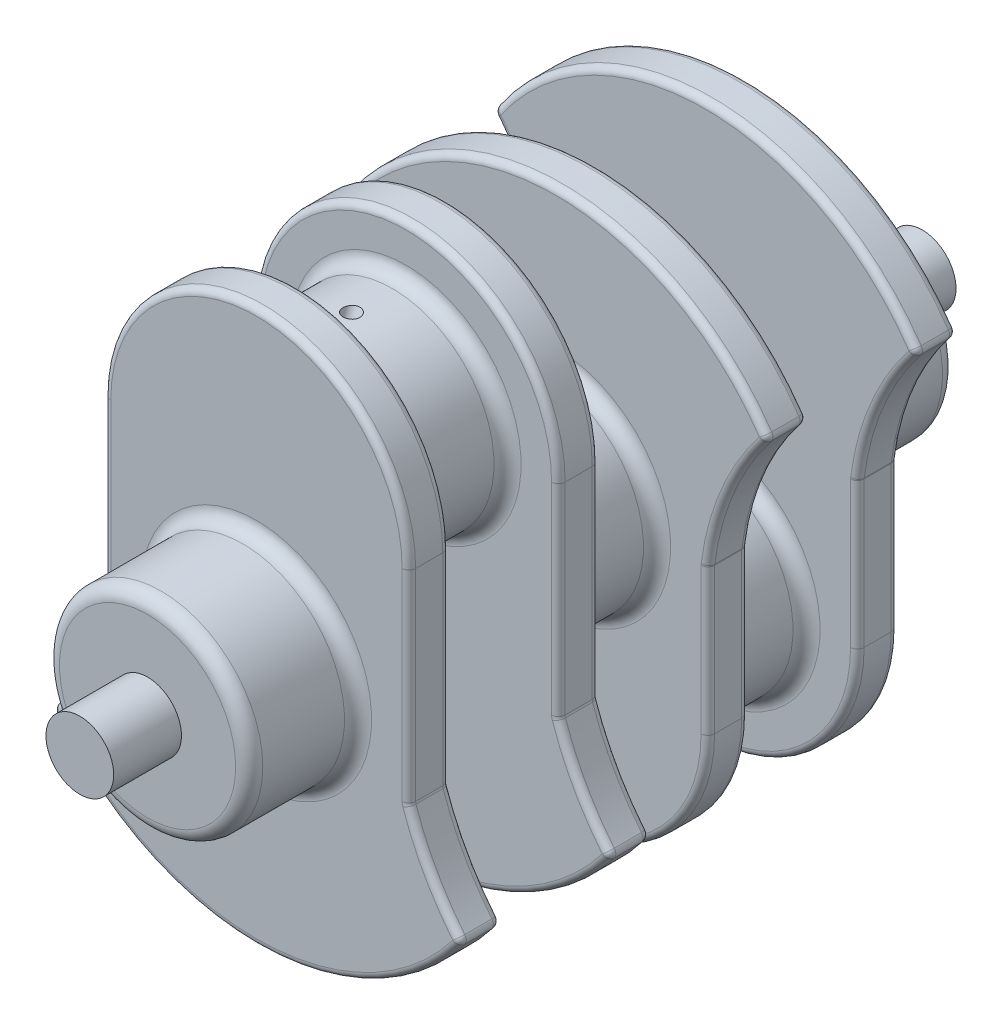
SolidWorks part; units mm, degrees
material "AISI 4340 Steel, normalized"
ref_plane "Front Plane" through (0, 0, 0) normal (0, 0, 1) x (1, 0, 0)
ref_plane "Top Plane" through (0, 0, 0) normal (0, 1, 0) x (1, 0, 0)
ref_plane "Right Plane" through (0, 0, 0) normal (1, 0, 0) x (0, 0, -1)
sketch "Sketch1" plane through (0, 0, 0) normal (0, 0, 1) x (1, 0, 0)
  circle A0 centre (0, 0) radius 30
  dimension "D1" = 30
extrude "Boss-Extrude1" add sketch "Sketch1" along normal blind 32.13
sketch "Sketch8" plane through (0, 0, 0) normal (0, 0, -1) x (-1, 0, 0)
  line L0 (-45, 43.2) -> (-45, -16.687)
  line L1 (45, 43.2) -> (45, -16.687)
  arc A0 (45, 43.2) -> (-45, 43.2) centre (0, 43.2) ccw
  arc A5 (-60.4975, -44.3289) -> (60.4975, -44.3289) centre (0, 0) ccw
  arc A6 (-45, -16.687) -> (-60.4975, -44.3289) centre (-125, 10) cw
  arc A7 (45, -16.687) -> (60.4975, -44.3289) centre (125, 10) ccw
  dimension "D1" = 45
  dimension "D2" = 75
  dimension "D3" = 43.2
  dimension "D5" = 10
  dimension "D6" = 125
extrude "Boss-Extrude5" add sketch "Sketch8" along normal blind 12
sketch "Sketch2" plane through (0, 0, 32.13) normal (0, 0, 1) x (1, 0, 0)
  circle A0 centre (0, 0) radius 10
  dimension "D1" = 10
extrude "Boss-Extrude2" add sketch "Sketch2" along normal blind 20
sketch "Sketch9" plane through (0, 0, -12) normal (0, 0, -1) x (-1, 0, 0)
  circle A0 centre (0, 43.2) radius 30
  dimension "D2" = 30
  dimension "D1" = 43.2
extrude "Boss-Extrude6" add sketch "Sketch9" along normal blind 32.13
ref_plane "Plane4" through (0, 0, -88.26) normal (0, 0, -1) x (-1, 0, 0)
sketch "Sketch10" plane through (0, 0, -44.13) normal (0, 0, -1) x (-1, 0, 0)
  line L0 (-45, -43.2) -> (-45, 0)
  line L1 (45, -43.2) -> (45, 0)
  arc A0 (-45, -43.2) -> (45, -43.2) centre (0, -43.2) ccw
  arc A1 (-45, 0) -> (-62.6932, 41.1651) centre (-125, -10) ccw
  arc A2 (45, 0) -> (62.6932, 41.1651) centre (125, -10) cw
  arc A3 (-62.6932, 41.1651) -> (62.6932, 41.1651) centre (0, 0) cw
  dimension "D1" = 45
  dimension "D5" = 10
  dimension "D3" = 75
  dimension "D2" = 43.2
  dimension "D4" = 125
extrude "Boss-Extrude7" add sketch "Sketch10" along normal blind 12 from surface starting at plane "Plane4"
ref_plane "Plane3" through (0, 0, -132.39) normal (0, 0, -1) x (-1, 0, 0)
sketch "Sketch12" plane through (0, 0, -132.39) normal (0, 0, -1) x (-1, 0, 0)
  line L2 (45, -43.2) -> (45, 0)
  line L3 (45, -43.2) -> (45, 0)
  line L4 (-45, 0) -> (-45, -43.2)
  line L5 (-45, 0) -> (-45, -43.2)
  arc A12 (-45, -43.2) -> (45, -43.2) centre (0, -43.2) ccw
  arc A13 (62.6932, 41.1651) -> (45, 0) centre (125, -10) ccw
  arc A14 (62.6932, 41.1651) -> (-62.6932, 41.1651) centre (0, 0) ccw
  arc A15 (-45, 0) -> (-62.6932, 41.1651) centre (-125, -10) ccw
  arc A16 (-45, -43.2) -> (45, -43.2) centre (0, -43.2) ccw
  arc A17 (62.6932, 41.1651) -> (45, 0) centre (125, -10) ccw
  arc A18 (62.6932, 41.1651) -> (-62.6932, 41.1651) centre (0, 0) ccw
  arc A19 (-45, 0) -> (-62.6932, 41.1651) centre (-125, -10) ccw
  dimension "D1" = 0
extrude "Boss-Extrude8" add sketch "Sketch12" along normal blind 12
sketch "Sketch14" plane through (0, 0, -100.26) normal (0, 0, -1) x (-1, 0, 0)
  circle A0 centre (0, -43.2) radius 30
  dimension "D2" = 30
  dimension "D1" = 43.2
extrude "Boss-Extrude9" add sketch "Sketch14" along normal up to next
sketch "Sketch15" plane through (0, 0, -144.39) normal (0, 0, -1) x (-1, 0, 0)
  circle A1 centre (0, 0) radius 30
  circle A2 centre (0, 0) radius 30
  dimension "D1" = 0
extrude "Boss-Extrude10" add sketch "Sketch15" along normal blind 32.13
sketch "Sketch16" plane through (0, 0, -176.52) normal (0, 0, -1) x (-1, 0, 0)
  circle A1 centre (0, 0) radius 10
  circle A2 centre (0, 0) radius 10
  dimension "D1" = 0
extrude "Boss-Extrude11" add sketch "Sketch16" along normal blind 20
sketch "Sketch18" plane through (0, 0, -44.13) normal (0, 0, -1) x (-1, 0, 0)
  line L2 (-45, 43.2) -> (-45, -16.687)
  line L3 (-45, 43.2) -> (-45, -16.687)
  line L4 (45, -16.687) -> (45, 43.2)
  line L5 (45, -16.687) -> (45, 43.2)
  arc A4 (45, 43.2) -> (-45, 43.2) centre (0, 43.2) ccw
  arc A5 (-60.4975, -44.3289) -> (-45, -16.687) centre (-125, 10) ccw
  arc A6 (-60.4975, -44.3289) -> (60.4975, -44.3289) centre (0, 0) ccw
  arc A7 (45, -16.687) -> (60.4975, -44.3289) centre (125, 10) ccw
  arc A8 (45, 43.2) -> (-45, 43.2) centre (0, 43.2) ccw
  arc A9 (-60.4975, -44.3289) -> (-45, -16.687) centre (-125, 10) ccw
  arc A10 (-60.4975, -44.3289) -> (60.4975, -44.3289) centre (0, 0) ccw
  arc A11 (45, -16.687) -> (60.4975, -44.3289) centre (125, 10) ccw
  dimension "D1" = 0
extrude "Boss-Extrude12" add sketch "Sketch18" along normal blind 12
sketch "Sketch19" plane through (0, 0, -56.13) normal (0, 0, -1) x (-1, 0, 0)
  circle A1 centre (0, 0) radius 30
  circle A2 centre (0, 0) radius 30
  dimension "D1" = 0
extrude "Boss-Extrude13" add sketch "Sketch19" along normal up to next
fillet "Fillet1" radius 2 32 edges at (0, -75, -44.13) (-51.4387, -31.2424, -44.13) (-45, 13.2565, -44.13) (45, 13.2565, -44.13) (51.4387, -31.2424, -44.13) (0, -75, -56.13) (-51.4387, -31.2424, -56.13) (-45, 13.2565, -56.13) (0, 88.2, -56.13) (45, 13.2565, -56.13) (51.4387, -31.2424, -56.13) (60.4975, -44.3289, -50.13) (45, -16.687, -50.13) (-45, -16.687, -50.13) (-60.4975, -44.3289, -50.13) (0, 88.2, -44.13) (45, 13.2565, 0) (51.4387, -31.2424, 0) (0, -75, 0) (-51.4387, -31.2424, 0) (-45, 13.2565, 0) (0, 88.2, -12) (45, 13.2565, -12) (51.4387, -31.2424, -12) (0, -75, -12) (-51.4387, -31.2424, -12) (-45, 13.2565, -12) (-45, -16.687, -6) (-60.4975, -44.3289, -6) (60.4975, -44.3289, -6) (45, -16.687, -6) (0, 88.2, 0)
fillet "Fillet2" radius 2 16 edges at (0, 75, -132.39) (50.9294, 21.8364, -132.39) (45, -21.6, -132.39) (0, -88.2, -132.39) (-45, -21.6, -132.39) (-50.9294, 21.8364, -132.39) (50.9294, 21.8364, -144.39) (45, -21.6, -144.39) (0, -88.2, -144.39) (-45, -21.6, -144.39) (-50.9294, 21.8364, -144.39) (-62.6932, 41.1651, -138.39) (-45, 0, -138.39) (45, 0, -138.39) (62.6932, 41.1651, -138.39) (0, 75, -144.39)
fillet "Fillet3" radius 2 16 edges at (45, -21.6, -88.26) (50.9294, 21.8364, -88.26) (0, 75, -88.26) (-50.9294, 21.8364, -88.26) (-45, -21.6, -88.26) (0, -88.2, -88.26) (45, -21.6, -100.26) (50.9294, 21.8364, -100.26) (-50.9294, 21.8364, -100.26) (-45, -21.6, -100.26) (0, -88.2, -100.26) (45, 0, -94.26) (62.6932, 41.1651, -94.26) (-62.6932, 41.1651, -94.26) (-45, 0, -94.26) (0, 75, -100.26)
fillet "Fillet5" radius 4 2 edges at (30, 0, 32.13) (30, 0, 0)
fillet "Fillet6" radius 4 2 edges at (-30, 0, -144.39) (-30, 0, -176.52)
ref_plane "Plane5" through (0, 31.75, 0) normal (0, 1, 0) x (1, 0, 0)
sketch "Sketch20" plane through (0, 0, 0) normal (1, 0, 0) x (0, 0, -1)
  line L1 (100.26, -73.2) -> (100.26, -13.2)
  line L2 (100.26, -73.2) -> (100.26, -13.2)
  dimension "D1" = 0
ref_plane "Plane6" through (0, -73.2, 0) normal (0, 1, 0) x (1, 0, 0)
sketch "Sketch21" plane through (0, 31.75, 0) normal (0, 1, 0) x (1, 0, 0)
  line L2 (-30, 172.52) -> (30, 172.52) construction
  line L3 (-30, 172.52) -> (-30, 148.39) construction
  line L4 (-30, 148.39) -> (30, 148.39) construction
  line L5 (30, 172.52) -> (30, 148.39) construction
  circle A0 centre (0, 160.455) radius 2.5
  point P10 (0, 172.52)
  point P11 (30, 160.455)
  dimension "D1" = 5
sketch "Sketch27" plane through (0, 0, 0) normal (0, 0, 1) x (1, 0, 0)
  line L0 (0, 73.2) -> (0, -30) construction
  circle A1 centre (0, 43.2) radius 30
  circle A2 centre (0, 43.2) radius 30 construction
  circle A3 centre (0, 0) radius 30
  circle A4 centre (0, 0) radius 30 construction
  dimension "D1" = 0
  dimension "D2" = 0
ref_plane "Plane8" through (0, 73.2, 0) normal (0, -1, 0) x (-1, 0, 0)
ref_plane "Plane9" through (0, -30, 0) normal (0, -1, 0) x (-1, 0, 0)
sketch "Sketch28" plane through (0, -30, 0) normal (0, -1, 0) x (-1, 0, 0)
  line L1 (-30, -4) -> (30, -4) construction
  line L2 (-30, -4) -> (-30, -28.13) construction
  line L3 (-30, -28.13) -> (30, -28.13) construction
  line L4 (30, -4) -> (30, -28.13) construction
  line L5 (-30, -4) -> (30, -28.13) construction
  line L6 (-30, -28.13) -> (30, -4) construction
  circle A0 centre (0, -16.065) radius 2.5
  point P4 (0, -16.065)
  dimension "D1" = 5
sketch "Sketch29" plane through (0, 73.2, 0) normal (0, -1, 0) x (-1, 0, 0)
  line L1 (30, 44.13) -> (-30, 44.13) construction
  line L2 (30, 44.13) -> (30, 12) construction
  line L3 (30, 12) -> (-30, 12) construction
  line L4 (-30, 44.13) -> (-30, 12) construction
  line L5 (30, 44.13) -> (-30, 12) construction
  line L6 (30, 12) -> (-30, 44.13) construction
  circle A0 centre (0, 28.065) radius 2.5
  point P4 (0, 28.065)
sketch "Sketch31" plane through (0, 0, 0) normal (1, 0, 0) x (0, 0, -1)
  line L0 (28.065, 73.2) -> (-16.065, -30) construction
ref_plane "Plane10" through (0, 73.2, -28.065) normal (0, -0.9195, 0.3932) x (-1, 0, 0)
ref_plane "Plane11" through (0, -30, 16.065) normal (0, -0.9195, 0.3932) x (-1, 0, 0)
combine bodies "Combine1" operation type add bodies to combine 119 109 117
fillet "Fillet7" radius 4 6 edges at (-30, 43.2, -44.13) (-30, 43.2, -12) (-30, 0, -56.13) (-30, 0, -88.26) (-30, -43.2, -132.39) (-30, -43.2, -100.26)
sketch "Sketch39" plane through (0, -73.2, 0) normal (0, 1, 0) x (1, 0, 0)
  line L1 (30, 128.39) -> (-30, 128.39) construction
  line L2 (30, 128.39) -> (30, 104.26) construction
  line L3 (30, 104.26) -> (-30, 104.26) construction
  line L4 (-30, 128.39) -> (-30, 104.26) construction
  line L5 (30, 128.39) -> (-30, 104.26) construction
  line L6 (30, 104.26) -> (-30, 128.39) construction
  point P4 (0, 116.325)
sketch "Sketch40" plane through (0, 0, 0) normal (1, 0, 0) x (0, 0, -1)
  line L0 (160.455, 31.75) -> (116.325, -73.2) construction
  line L1 (172.52, 31.75) -> (148.39, 31.75) construction
ref_plane "Plane12" through (0, 31.75, -160.455) normal (0, -0.9218, 0.3876) x (-1, 0, 0)
ref_plane "Plane13" through (0, -73.2, -116.325) normal (0, -0.9218, 0.3876) x (-1, 0, 0)
sketch "Sketch47" plane through (0, 73.2, -28.065) normal (0, -0.9195, 0.3932) x (-1, 0, 0)
  ellipse E0 centre (0, 0) end of major axis (2.5, 0) minor radius 2.2987 construction
  ellipse E1 centre (0, 0) end of major axis (2.5, 0) minor radius 2.2987
extrude "Cut-Extrude1" cut sketch "Sketch47" along normal through all
sketch "Sketch48" plane through (0, -30, 16.065) normal (0, -0.9195, 0.3932) x (-1, 0, 0)
  ellipse E0 centre (0, 0) end of major axis (2.5, 0) minor radius 2.2987 construction
  ellipse E1 centre (0, 0) end of major axis (2.5, 0) minor radius 2.2987
extrude "Cut-Extrude2" cut sketch "Sketch48" against normal through all
sketch "Sketch49" plane through (0, -73.2, -116.325) normal (0, -0.9218, 0.3876) x (-1, 0, 0)
  circle A0 centre (0, 0) radius 2.5
  dimension "D1" = 5
extrude "Cut-Extrude3" cut sketch "Sketch49" against normal through all
sketch "Sketch50" plane through (0, 31.75, -160.455) normal (0, -0.9218, 0.3876) x (-1, 0, 0)
  circle A0 centre (0, 0) radius 2.5 construction
  circle A1 centre (0, 0) radius 2.5
extrude "Cut-Extrude4" cut sketch "Sketch50" along normal through all
equation "\"CRR\"= 43.2mm'Crank Radius"
equation "\"D1@Sketch9\"=\"CRR\""
equation "\"D1@Sketch14\"=\"CRR\""
equation "\"JR\"= 30mm'Journal Radius"
equation "\"D1@Sketch1\"=\"JR\""
equation "\"D2@Sketch9\"=\"JR\""
equation "\"D2@Sketch14\"=\"JR\""
equation "\"LT\"= 12mm'Lobe Thickness"
equation "\"D1@Boss-Extrude5\"=\"LT\""
equation "\"D1@Boss-Extrude7\"=\"LT\""
equation "\"D1@Boss-Extrude8\"=\"LT\""
equation "\"D1@Boss-Extrude12\"=\"LT\""
equation "\"D3@Sketch8\"=\"CRR\""
equation "\"D2@Sketch10\"=\"CRR\""
equation "\"JL\"= 24.13 + 2 * ( \"JF\" )'Journal Length"
equation "\"D1@Boss-Extrude1\"=\"JL\""
equation "\"D1@Boss-Extrude6\"=\"JL\""
equation "\"D1@Boss-Extrude10\"=\"JL\""
equation "\"LHD\"= 5mm'Lubrication Hole Diameter"
equation "\"D1@Sketch29\"=\"LHD\""
equation "\"JF\"= 4mm'Internal Journal Fillets"
equation "\"D1@Fillet7\"=\"JF\""
equation "\"D1@Fillet6\"=\"JF\""
equation "\"LR\"= 45mm'Lobe radius"
equation "\"CWR\"= 75mm'Counterweight Radius"
equation "\"D1@Sketch8\"=\"LR\""
equation "\"D2@Sketch8\"=\"CWR\""
equation "\"D3@Sketch10\"=\"CWR\""
equation "\"D1@Sketch10\"=\"LR\""
